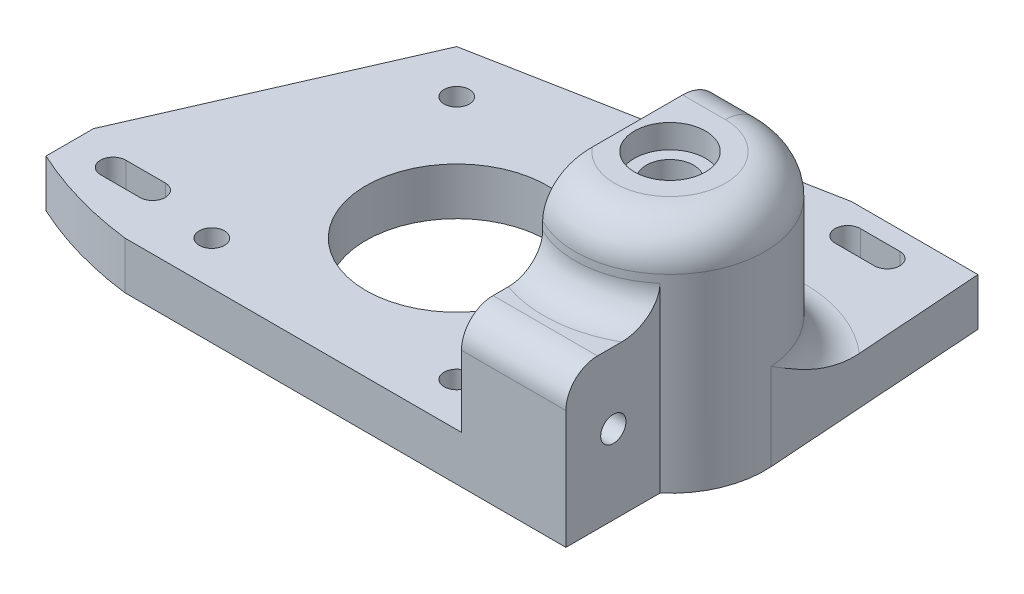
SolidWorks part; units mm, degrees
ref_plane "Front Plane" through (0, 0, 0) normal (0, 0, 1) x (1, 0, 0)
ref_plane "Top Plane" through (0, 0, 0) normal (0, 1, 0) x (1, 0, 0)
ref_plane "Right Plane" through (0, 0, 0) normal (1, 0, 0) x (0, 0, -1)
sketch "Sketch1" plane through (0, 0, 0) normal (0, 1, 0) x (1, 0, 0)
  line L3 (0, 0) -> (27, 0) construction
  line L8 (21, 21) -> (34.8293, 9.0941) construction
  line L9 (21, -21) -> (34.8293, -9.0941) construction
  line L10 (-21, 21) -> (21, 29)
  line L11 (21, 29) -> (33, 29)
  line L12 (-21, -21) -> (21, -21)
  line L13 (33, 29) -> (33, 10.6689) construction
  line L14 (21, 29) -> (21, 21) construction
  line L15 (24.5, 25) -> (29.5, 25) construction
  line L16 (24.5, 26.6) -> (29.5, 26.6)
  line L17 (33, 29) -> (37, 29)
  line L18 (-35, -17) -> (-35, -11)
  line L19 (-35, -11) -> (-21, 21)
  line L20 (37, 29) -> (38.9707, 0.8377)
  line L22 (34.8293, -9.0941) -> (34.8293, -21)
  line L23 (34.8293, -21) -> (21, -21)
  line L24 (24.5, 23.4) -> (29.5, 23.4)
  line L28 (-21, -21) -> (-21, 21) construction
  line L29 (-21, 21) -> (21, 21) construction
  line L30 (21, -21) -> (21, 21) construction
  line L31 (-21, -21) -> (21, 21) construction
  line L32 (-21, 21) -> (21, -21) construction
  line L33 (-15.5, 15.5) -> (15.5, 15.5) construction
  line L34 (-15.5, 15.5) -> (-15.5, -15.5) construction
  line L35 (-15.5, -15.5) -> (15.5, -15.5) construction
  line L36 (15.5, 15.5) -> (15.5, -15.5) construction
  line L37 (27, 25) -> (27, 29) construction
  line L38 (24.5, 25) -> (21, 25) construction
  line L39 (-29.5, -14) -> (-24.5, -14) construction
  line L40 (-29.5, -12.4) -> (-24.5, -12.4)
  line L41 (-29.5, -15.6) -> (-24.5, -15.6)
  line L42 (-21, 21) -> (-21, 26) construction
  line L43 (37, 29) -> (33, 29)
  circle A0 centre (27, 0) radius 20 construction
  circle A1 centre (-15.5, 15.5) radius 1.6
  circle A2 centre (27, 0) radius 3
  circle A4 centre (27, 0) radius 8 construction
  arc A6 (34.8293, -9.0941) -> (34.8293, 9.0941) centre (27, 0) ccw
  arc A9 (24.5, 26.6) -> (24.5, 23.4) centre (24.5, 25) ccw
  circle A10 centre (15.5, 15.5) radius 1.6
  circle A11 centre (15.5, -15.5) radius 1.6
  circle A12 centre (-15.5, -15.5) radius 1.6
  circle A13 centre (0, 0) radius 11.5
  arc A14 (29.5, 23.4) -> (29.5, 26.6) centre (29.5, 25) ccw
  arc A15 (-29.5, -12.4) -> (-29.5, -15.6) centre (-29.5, -14) ccw
  arc A16 (-24.5, -15.6) -> (-24.5, -12.4) centre (-24.5, -14) ccw
  arc A19 (-35, -17) -> (-21, -21) centre (-15.2439, 25.6462) ccw
  point P11 (27, 25)
  point P14 (0, 0)
  point P30 (-27, -14)
  dimension "D4" = 40
  dimension "D6" = 12
  dimension "D8" = 12
  dimension "D10" = 1.6
  dimension "D12" = 1.6
  dimension "D18" = 3.2
  dimension "D19" = 3.2
  dimension "D20" = 3.2
  dimension "D21" = 3.2
  dimension "D22" = 23
  dimension "D5" = 6
  dimension "D7" = 16
  dimension "D11" = 5
  dimension "D25" = 6
  dimension "D13" = 47
  dimension "D3" = 27
  dimension "D9" = 8
  dimension "D14" = 5
  dimension "D15" = 42
  dimension "D16" = 42
  dimension "D17" = 31
  dimension "D23" = 14
  dimension "D24" = 4
  dimension "D26" = 16
  dimension "D27" = 6
extrude "Boss-Extrude1" add sketch "Sketch1" along normal blind 6 contours L9 A6 L11 L10 L19 L18 L12 A13 A12 A11 A10 A1 A2 region at (0.1671, 0, -24.1227)
sketch "Sketch2" plane through (0, 0, 0) normal (0, 1, 0) x (1, 0, 0)
  circle A0 centre (27, 0) radius 8
  dimension "D1" = 16
extrude "Cut-Extrude1" cut sketch "Sketch2" along normal blind 5
sketch "Sketch3" plane through (0, 6, 0) normal (0, 1, 0) x (1, 0, 0)
  line L0 (21.6, -21) -> (34.8293, -21)
  line L5 (21.6, -21) -> (21.6, 12)
  line L11 (34.8293, -9.0941) -> (34.8293, -21)
  line L15 (27, 12) -> (21.6, 12)
  circle A8 centre (27, 0) radius 3
  arc A9 (34.8293, -9.0941) -> (27, 12) centre (27, 0) ccw
  arc A10 (34.8293, -9.0941) -> (38.9707, 0.8377) centre (27, 0) ccw construction
  dimension "D1" = 21.6
extrude "Boss-Extrude2" add sketch "Sketch3" along normal blind 23
sketch "Sketch4" plane through (0, 29, 0) normal (0, 1, 0) x (1, 0, 0)
  circle A0 centre (27, 0) radius 4.5
  dimension "D1" = 9
extrude "Cut-Extrude2" cut sketch "Sketch4" against normal blind 3
sketch "Sketch5" plane through (0, 0, 0) normal (0, -1, 0) x (1, 0, 0)
  circle A0 centre (15.5, 15.5) radius 3
  circle A1 centre (-15.5, -15.5) radius 3
  circle A2 centre (-15.5, 15.5) radius 3
  circle A3 centre (15.5, -15.5) radius 3
  dimension "D1" = 6
  dimension "D2" = 6
  dimension "D3" = 6
  dimension "D4" = 6
extrude "Cut-Extrude3" cut sketch "Sketch5" against normal blind 2
sketch "Sketch6" plane through (34.8293, 0, 0) normal (1, 0, 0) x (0, 0, -1)
  line L0 (-15, 29) -> (-15, 0) construction
  line L1 (-21, 29) -> (-9.0941, 29) construction
  line L2 (-9.0941, 0) -> (-21, 0) construction
  line L4 (-21, 29) -> (-21, 0) construction
  line L5 (12, 6) -> (0.8377, 6) construction
  circle A0 centre (-15, 10) radius 1.6
  dimension "D1" = 3.2
  dimension "D2" = 4
  dimension "D3" = 6
extrude "Cut-Extrude4" cut sketch "Sketch6" against normal through all and the other way through all
sketch "Sketch7" plane through (21.6, 0, 0) normal (-1, 0, 0) x (0, 0, 1)
  line L1 (18.1754, 10) -> (16.5877, 12.75)
  line L2 (16.5877, 12.75) -> (13.4123, 12.75)
  line L3 (13.4123, 12.75) -> (11.8246, 10)
  line L4 (11.8246, 10) -> (13.4123, 7.25)
  line L5 (13.4123, 7.25) -> (16.5877, 7.25)
  line L6 (16.5877, 7.25) -> (18.1754, 10)
  circle A0 centre (15, 10) radius 2.75 construction
  dimension "D1" = 5.5
extrude "Cut-Extrude5" cut sketch "Sketch7" against normal blind 10
fillet "Fillet1" radius 5 2 edges at (24.3, 6, -12) (35.1838, 6, -8.7765)
sketch "Sketch8" plane through (0, 29, 0) normal (0, 1, 0) x (1, 0, 0)
  line L0 (21, -10.3923) -> (21.6, -21)
  line L4 (27, 12) -> (21.6, 12)
  line L5 (21.6, 12) -> (21.6, -21)
  line L6 (21.6, -21) -> (34.8293, -21)
  line L7 (34.8293, -21) -> (34.8293, -9.0941)
  line L10 (21.6, -21) -> (34.8293, -21)
  line L11 (34.8293, -21) -> (34.8293, -9.0941)
  arc A1 (21, -10.3923) -> (34.8293, -9.0941) centre (27, 0) ccw
  arc A2 (34.8293, -9.0941) -> (27, 12) centre (27, 0) ccw
  dimension "D1" = 0
extrude "Cut-Extrude6" cut sketch "Sketch8" against normal blind 10
fillet "Fillet2" radius 5 2 edges at (24.3, 29, -12) (38.6747, 29, 2.7752)
fillet "Fillet3" radius 4 2 edges at (28.4606, 19, 11.9108) (28.2146, 19, 21)
